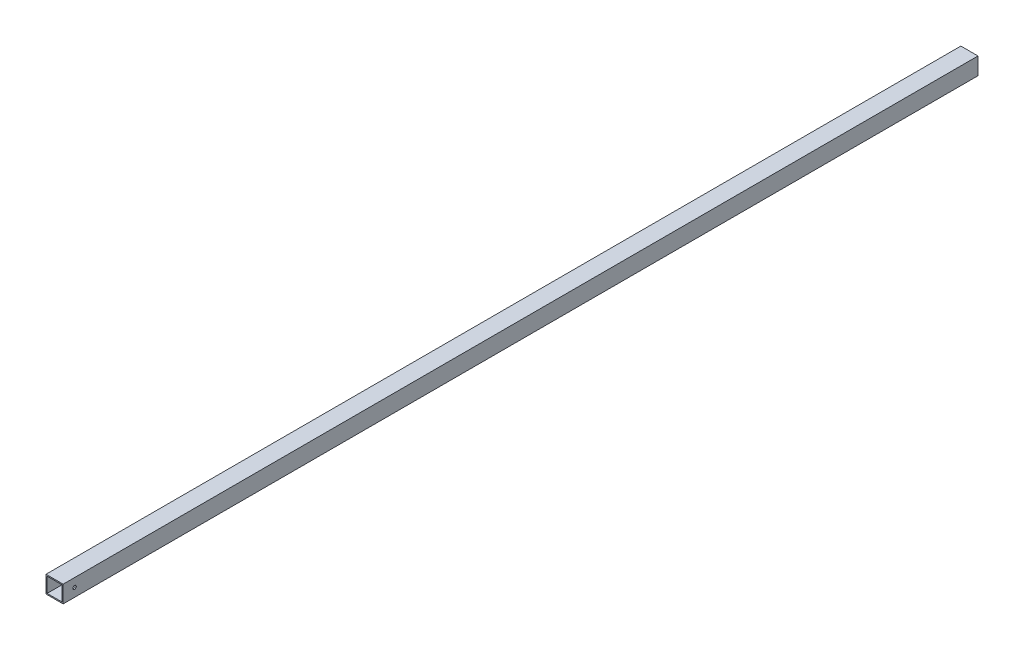
SolidWorks part; units mm, degrees
material "1060 合金"
ref_plane "前视基准面" through (0, 0, 0) normal (0, 0, 1) x (1, 0, 0)
ref_plane "上视基准面" through (0, 0, 0) normal (0, 1, 0) x (1, 0, 0)
ref_plane "右视基准面" through (0, 0, 0) normal (1, 0, 0) x (0, 0, -1)
other "Configuration Table"
sketch "草图1" plane through (0, 0, 0) normal (0, 0, 1) x (1, 0, 0)
  line L1 (0, 0) -> (15, 0)
  line L2 (0, 0) -> (0, -15)
  line L3 (0, -15) -> (15, -15)
  line L4 (15, 0) -> (15, -15)
  dimension "D1" = 15
  dimension "D2" = 15
extrude "拉伸-薄壁1" add sketch "草图1" along normal blind 800 thin thin type one direction reverse wall 1
sketch "草图2" plane through (0, -15, 0) normal (0, -1, 0) x (1, 0, 0)
  circle A1 centre (7.5, 825) radius 2.6
  circle A2 centre (7.5, 825) radius 2.6
  dimension "D1" = 0
extrude "切除-拉伸1" [suppressed] cut sketch "草图2" against normal up to next
sketch "草图3" plane through (0, 0, 0) normal (-1, 0, 0) x (0, 0, 1)
  line L0 (800, 0) -> (0, 0) construction
  line L1 (0, 0) -> (0, -15) construction
  circle A0 centre (215, -7.5) radius 1.7
  circle A1 centre (170, -7.5) radius 1.7
  dimension "D1" = 3.4
  dimension "D2" = 3.4
  dimension "D3" = 45
  dimension "D4" = 7.5
  dimension "D5" = 7.5
  dimension "D6" = 170
sketch "草图4" plane through (15, 0, 0) normal (1, 0, 0) x (0, 0, -1)
  line L0 (-800, -15) -> (0, -15) construction
  line L1 (-800, -15) -> (-800, 0) construction
  circle A0 centre (-790, -7.5) radius 1.5
  dimension "D1" = 3
  dimension "D2" = 7.5
  dimension "D3" = 10
extrude "切除-拉伸3" cut sketch "草图4" against normal through all
